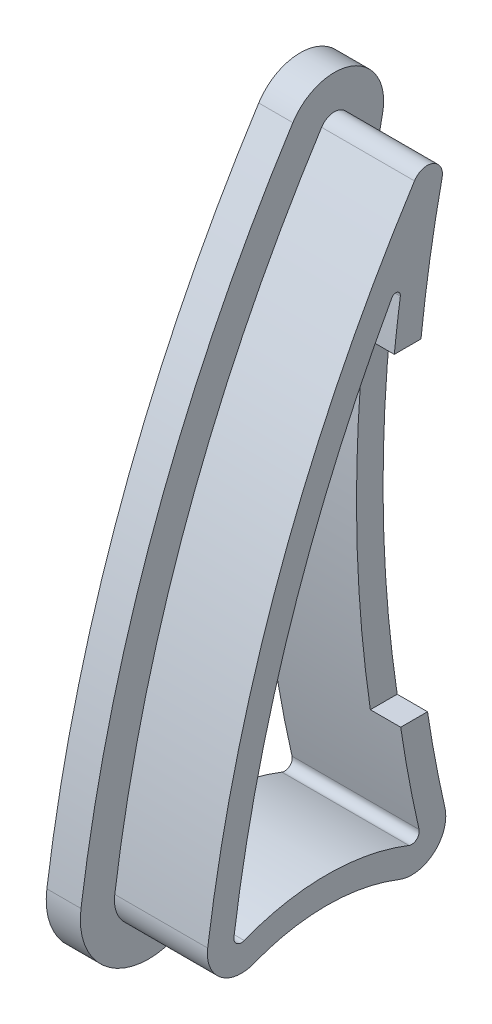
SolidWorks part; units mm, degrees
ref_plane "Front Plane" through (0, 0, 0) normal (0, 0, 1) x (1, 0, 0)
ref_plane "Top Plane" through (0, 0, 0) normal (0, 1, 0) x (1, 0, 0)
ref_plane "Right Plane" through (0, 0, 0) normal (1, 0, 0) x (0, 0, -1)
sketch "Sketch1" plane through (0, 0, 0) normal (0, 0, 1) x (1, 0, 0)
  line L0 (0, 0) -> (0, -27.8746) construction
  line L1 (-15.5575, 76.2) -> (15.5575, 76.2)
  line L2 (-15.5575, 76.2) -> (-15.5575, -76.2)
  line L3 (-15.5575, -76.2) -> (-7.8455, -76.2)
  line L4 (15.5575, 76.2) -> (15.5575, -76.2)
  line L5 (-15.5575, 76.2) -> (15.5575, -76.2) construction
  line L6 (-15.5575, -76.2) -> (15.5575, 76.2) construction
  line L7 (7.8455, -76.2) -> (9.525, -85.725)
  line L8 (-7.8455, -76.2) -> (-9.525, -85.725)
  line L9 (-9.525, -85.725) -> (9.525, -85.725)
  line L10 (7.8455, -76.2) -> (15.5575, -76.2)
  point P0 (0, 0)
  point P12 (0, -85.725)
  dimension "D1" = 31.115
  dimension "D2" = 152.4
  dimension "D3" = 20
  dimension "D4" = 19.05
  dimension "D5" = 9.525
extrude "Boss-Extrude1" add sketch "Sketch1" along normal blind 76.2
sketch "Sketch2" plane through (15.5575, 0, 0) normal (1, 0, 0) x (0, 0, -1)
  line L0 (-76.2, -76.2) -> (0, -76.2) construction
  line L1 (0, -85.725) -> (-6.985, -85.725)
  line L2 (0, -85.725) -> (0, -76.2)
  line L3 (0, -76.2) -> (-6.985, -76.2)
  line L4 (-6.985, -85.725) -> (-6.985, -76.2)
  dimension "D1" = 6.985
extrude "Cut-Extrude1" cut sketch "Sketch2" against normal through all
sketch "Sketch3" plane through (15.5575, 0, 0) normal (1, 0, 0) x (0, 0, -1)
  line L14 (-76.2, 76.2) -> (0, 76.2) construction
  line L15 (-76.2, -76.2) -> (-76.2, 76.2) construction
  line L16 (-76.2, -85.725) -> (-76.2, -76.2) construction
  line L17 (0, -76.2) -> (0, 76.2) construction
  line L18 (-76.2, -85.725) -> (-76.2, -76.2)
  line L19 (-76.2, -76.2) -> (-76.2, 76.2)
  line L20 (-76.2, 76.2) -> (-15.9075, 76.2)
  line L21 (0, -76.2) -> (0, 63.7964)
  arc A4 (-15.9075, 76.2) -> (-76.2, -85.725) centre (171.3838, -85.725) ccw
  arc A5 (0, 63.7964) -> (0, -76.2) centre (184.1989, -6.2018) ccw
  point P4 (-10.0952, 76.2)
  point P5 (0, 60.6261)
  point P6 (0, 50.0582)
  point P9 (-10.3594, 76.2)
  point P11 (0, 63.7964)
  point P12 (-15.9075, 76.2)
extrude "Cut-Extrude2" cut sketch "Sketch3" against normal through all
sketch "Sketch6" plane through (15.5575, 0, 0) normal (1, 0, 0) x (0, 0, -1)
  line L8 (-61.7469, -62.865) -> (-18.4126, -62.865)
  arc A2 (-26.0044, 40.4114) -> (-21.3821, 38.504) centre (-23.8641, 39.0437) cw
  arc A3 (-28.5756, -59.6454) -> (-20.9027, -53.058) centre (-26.4741, -54.3308) ccw
  arc A14 (-17.8942, 52.2835) -> (-61.7469, -62.865) centre (171.3838, -85.725) ccw
  arc A15 (-17.8942, 52.2835) -> (-18.4126, -62.865) centre (184.1989, -6.2018) ccw
  arc A16 (-26.0044, 40.4114) -> (-60.6442, -53.5457) centre (171.3838, -85.725) ccw
  arc A17 (-21.3821, 38.504) -> (-20.9027, -53.058) centre (184.1989, -6.2018) ccw
  arc A18 (-60.6442, -53.5457) -> (-52.8819, -59.6454) centre (-54.9834, -54.3308) ccw
  arc A19 (-52.8819, -59.6454) -> (-28.5756, -59.6454) centre (-40.7287, -90.3804) cw
  point P10 (0, 0)
  dimension "D2" = 2.54
  dimension "D3" = 5.715
  dimension "D1" = 13.335
extrude "Cut-Extrude3" cut sketch "Sketch6" against normal through all
sketch "Sketch7" plane through (0, 0, 0) normal (1, 0, 0) x (0, 0, -1)
  line L0 (-24.911, 16.933) -> (-11.489, 16.933)
  line L1 (-23.819, -37.677) -> (-10.3218, -37.677)
  arc A0 (0, 63.7964) -> (0, -76.2) centre (184.1989, -6.2018) ccw construction
  arc A1 (-21.3821, 38.504) -> (-20.9027, -53.058) centre (184.1989, -6.2018) ccw construction
  arc A2 (-24.911, 16.933) -> (-23.819, -37.677) centre (184.1989, -6.2018) ccw
  arc A3 (-11.489, 16.933) -> (-10.3218, -37.677) centre (184.1989, -6.2018) ccw
  point P3 (-12.8518, -6.2018)
  point P11 (0, 0)
  dimension "D1" = 54.61
extrude "Cut-Extrude4" cut sketch "Sketch7" against normal mid plane 10.16
sketch "Sketch9" plane through (15.5575, 0, 0) normal (1, 0, 0) x (0, 0, -1)
  line L0 (-15.9075, 76.2) -> (0, 63.7964)
ref_plane "Plane2" through (15.5575, 76.2, 15.9075) normal (0, -0.6149, -0.7886) x (-1, 0, 0)
sketch "Sketch10" plane through (15.5575, 76.2, 15.9075) normal (0, -0.6149, -0.7886) x (-1, 0, 0)
  line L4 (15.5575, 9.7815) -> (15.5575, 19.0294) construction
  line L5 (0, 9.7815) -> (31.115, 9.7815) construction
  line L6 (0, 9.7815) -> (8.255, 9.7815)
  line L7 (8.255, 9.7815) -> (0, -2.2835)
  line L8 (0, 0) -> (0, -110.402) construction
  line L9 (0, 9.7815) -> (0, -2.2835)
  line L10 (31.115, 9.7815) -> (31.115, -2.2835)
  line L11 (22.86, 9.7815) -> (31.115, -2.2835)
  line L12 (31.115, 9.7815) -> (22.86, 9.7815)
  point P2 (0, 0.955)
  dimension "D1" = 12.065
  dimension "D2" = 8.255
extrude "Cut-Extrude6" cut sketch "Sketch10" against normal mid plane 73.66
fillet "Fillet2" radius 0.762 5 edges at (-15.5575, 4.0516, 59.3496) (-14.7762, 75.3337, 16.653) (0, 76.2, 15.9075) (15.5575, 4.0516, 59.3496) (14.7762, 75.3337, 16.653)
sketch "Sketch11" plane through (15.5575, 0, 0) normal (1, 0, 0) x (0, 0, -1)
  arc A0 (-60.6442, -53.5457) -> (-52.8819, -59.6454) centre (-54.9834, -54.3308) ccw construction
  arc A1 (-28.5756, -59.6454) -> (-52.8819, -59.6454) centre (-40.7287, -90.3804) ccw construction
  arc A2 (-28.5756, -59.6454) -> (-20.9027, -53.058) centre (-26.4741, -54.3308) ccw construction
  arc A3 (-21.3821, 38.504) -> (-20.9027, -53.058) centre (184.1989, -6.2018) ccw construction
  arc A4 (-26.0044, 40.4114) -> (-60.6442, -53.5457) centre (171.3838, -85.725) ccw construction
  arc A5 (-21.3821, 38.504) -> (-26.0044, 40.4114) centre (-23.8641, 39.0437) ccw construction
  arc A6 (-60.6442, -53.5457) -> (-52.8819, -59.6454) centre (-54.9834, -54.3308) ccw
  arc A7 (-28.5756, -59.6454) -> (-52.8819, -59.6454) centre (-40.7287, -90.3804) ccw
  arc A8 (-28.5756, -59.6454) -> (-20.9027, -53.058) centre (-26.4741, -54.3308) ccw
  arc A9 (-21.3821, 38.504) -> (-20.9027, -53.058) centre (184.1989, -6.2018) ccw
  arc A10 (-26.0044, 40.4114) -> (-60.6442, -53.5457) centre (171.3838, -85.725) ccw
  arc A11 (-21.3821, 38.504) -> (-26.0044, 40.4114) centre (-23.8641, 39.0437) ccw
  arc A12 (-56.2413, -54.1563) -> (-54.5164, -55.5118) centre (-54.9834, -54.3308) ccw
  arc A13 (-26.9411, -55.5118) -> (-54.5164, -55.5118) centre (-40.7287, -90.3804) ccw
  arc A14 (-26.9411, -55.5118) -> (-25.236, -54.048) centre (-26.4741, -54.3308) ccw
  arc A15 (-27.7257, 29.0147) -> (-25.236, -54.048) centre (184.1989, -6.2018) ccw
  arc A16 (-27.7257, 29.0147) -> (-27.7257, 29.0147) centre (-27.7257, 29.0147) ccw
  arc A17 (-27.7257, 29.0147) -> (-56.2413, -54.1563) centre (171.3838, -85.725) ccw
  dimension "D1" = 4.445
extrude "Boss-Extrude2" add sketch "Sketch11" against normal blind 15.5575 separate body
fillet "Fillet3" radius 0.762 1 edges at (7.7787, 29.0147, 27.7257)
sketch "Sketch12" plane through (15.5575, 0, 0) normal (1, 0, 0) x (0, 0, -1)
  arc A28 (-56.2413, -54.1563) -> (-54.5164, -55.5118) centre (-54.9834, -54.3308) ccw construction
  arc A29 (-26.9411, -55.5118) -> (-54.5164, -55.5118) centre (-40.7287, -90.3804) ccw construction
  arc A30 (-26.9411, -55.5118) -> (-25.236, -54.048) centre (-26.4741, -54.3308) ccw construction
  arc A31 (-28.373, 24.8697) -> (-25.236, -54.048) centre (184.1989, -6.2018) ccw construction
  arc A32 (-29.794, 25.3482) -> (-56.2413, -54.1563) centre (171.3838, -85.725) ccw construction
  arc A33 (-28.373, 24.8697) -> (-29.794, 25.3482) centre (-29.127, 24.9799) ccw construction
  arc A34 (-56.2413, -54.1563) -> (-54.5164, -55.5118) centre (-54.9834, -54.3308) ccw
  arc A35 (-26.9411, -55.5118) -> (-54.5164, -55.5118) centre (-40.7287, -90.3804) ccw
  arc A36 (-26.9411, -55.5118) -> (-25.236, -54.048) centre (-26.4741, -54.3308) ccw
  arc A37 (-28.373, 24.8697) -> (-25.236, -54.048) centre (184.1989, -6.2018) ccw
  arc A38 (-29.794, 25.3482) -> (-56.2413, -54.1563) centre (171.3838, -85.725) ccw
  arc A39 (-28.373, 24.8697) -> (-29.794, 25.3482) centre (-29.127, 24.9799) ccw
  arc A52 (-30.8201, 43.4888) -> (-66.305, -52.7606) centre (171.3838, -85.725) ccw
  arc A53 (-66.305, -52.7606) -> (-50.7804, -64.96) centre (-54.9834, -54.3308) ccw
  arc A54 (-30.6771, -64.96) -> (-50.7804, -64.96) centre (-40.7287, -90.3804) ccw
  arc A55 (-30.6771, -64.96) -> (-15.3312, -51.7852) centre (-26.4741, -54.3308) ccw
  arc A56 (-15.7976, 37.2896) -> (-15.3312, -51.7852) centre (184.1989, -6.2018) ccw
  arc A57 (-15.7976, 37.2896) -> (-30.8201, 43.4888) centre (-23.8641, 39.0437) ccw
  arc A58 (-30.8201, 43.4888) -> (-66.305, -52.7606) centre (171.3838, -85.725) ccw
  arc A59 (-66.305, -52.7606) -> (-50.7804, -64.96) centre (-54.9834, -54.3308) ccw
  arc A60 (-30.6771, -64.96) -> (-50.7804, -64.96) centre (-40.7287, -90.3804) ccw
  arc A61 (-30.6771, -64.96) -> (-15.3312, -51.7852) centre (-26.4741, -54.3308) ccw
  arc A62 (-15.7976, 37.2896) -> (-15.3312, -51.7852) centre (184.1989, -6.2018) ccw
  arc A63 (-15.7976, 37.2896) -> (-30.8201, 43.4888) centre (-23.8641, 39.0437) ccw
  dimension "D1" = 5.715
extrude "Boss-Extrude3" add sketch "Sketch12" along normal blind 5.715
sketch "Sketch13" plane through (0, 0, 0) normal (1, 0, 0) x (0, 0, -1)
  line L0 (-11.489, 16.933) -> (-29.3825, 16.933)
  line L1 (-10.3218, -37.677) -> (-28.3136, -37.677)
  arc A0 (-28.373, 24.8697) -> (-25.236, -54.048) centre (184.1989, -6.2018) ccw construction
  arc A1 (-0.8368, 61.5534) -> (0, -76.2) centre (184.1989, -6.2018) ccw construction
  arc A2 (-29.3825, 16.933) -> (-28.3136, -37.677) centre (184.1989, -6.2018) ccw
  arc A3 (-11.489, 16.933) -> (-10.3218, -37.677) centre (184.1989, -6.2018) ccw
extrude "Cut-Extrude7" cut sketch "Sketch13" along normal blind 5.08
delete or keep bodies "Body-Delete/Keep 1" type delete bodies bodies 107
combine bodies "Combine1" operation type add bodies to combine 111 109
mirror "Mirror1" about plane through (0, -70.0279, -58.2002) normal (1, 0, 0) of bodies 110
delete or keep bodies "Body-Delete/Keep 2" type delete bodies bodies 110
